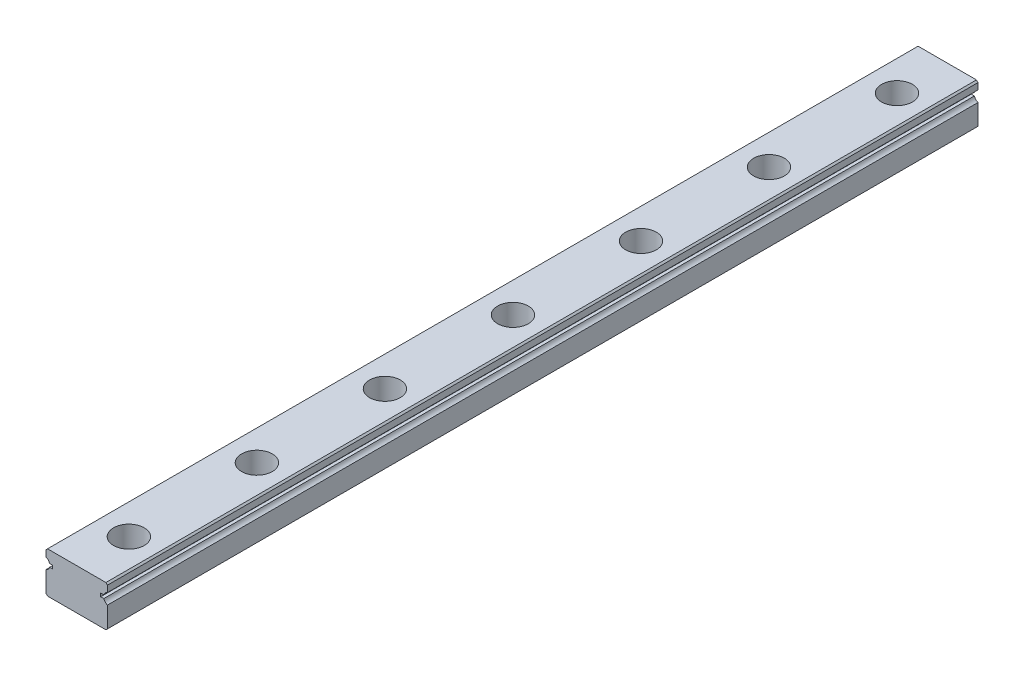
SolidWorks part; units mm, degrees
ref_plane "Спереди" through (0, 0, 0) normal (0, 0, 1) x (1, 0, 0)
ref_plane "Сверху" through (0, 0, 0) normal (0, 1, 0) x (1, 0, 0)
ref_plane "Справа" through (0, 0, 0) normal (1, 0, 0) x (0, 0, -1)
sketch "Эскиз1" plane through (0, 0, 0) normal (0, 0, 1) x (1, 0, 0)
  line L0 (-6, 3.7) -> (-5.7, 4)
  line L1 (-5.7, -4) -> (5.7, -4)
  line L2 (-6, -3.7) -> (-6, 0.3334)
  line L3 (-5.7, 4) -> (5.7, 4)
  line L4 (6, -3.7) -> (6, 0.3334)
  line L5 (-6, -4) -> (6, 4) construction
  line L6 (-6, 4) -> (6, -4) construction
  line L7 (-6, -3.7) -> (-5.7, -4)
  line L8 (5.7, -4) -> (6, -3.7)
  line L9 (5.7, 4) -> (6, 3.7)
  line L10 (-6, 2.4498) -> (-6, 3.7)
  line L11 (-5.2979, 1.7203) -> (-4.6875, 1.7203)
  line L12 (0, 5.4188) -> (0, -5.747) construction
  line L13 (-5.2922, 1.0823) -> (-4.6875, 1.0823)
  line L14 (-4.6875, 1.7203) -> (-4.6875, 1.0823)
  line L15 (4.6875, 1.7203) -> (4.6875, 1.0823)
  line L16 (5.2922, 1.0823) -> (4.6875, 1.0823)
  line L17 (5.2979, 1.7203) -> (4.6875, 1.7203)
  line L18 (6, 2.4498) -> (6, 3.7)
  arc A0 (-6, 0.3334) -> (-5.2922, 1.0823) centre (-6.3695, 1.3916) ccw
  arc A1 (-5.2979, 1.7203) -> (-6, 2.4498) centre (-6.3695, 1.3916) ccw
  arc A2 (5.2979, 1.7203) -> (6, 2.4498) centre (6.3695, 1.3916) cw
  arc A3 (6, 0.3334) -> (5.2922, 1.0823) centre (6.3695, 1.3916) cw
  point P0 (0, 0)
extrude "Бобышка-Вытянуть1" add sketch "Эскиз1" along normal blind 170
sketch "Эскиз2" plane through (0, 4, 0) normal (0, 1, 0) x (1, 0, 0)
  line L0 (0, 0) -> (0, -26.2396) construction
  line L1 (5.7, 0) -> (-5.7, 0) construction
  line L2 (-3.8306, -10) -> (4.207, -10) construction
  circle A0 centre (0.1882, -10) radius 3
  circle A1 centre (0.1882, -10) radius 1.75
  dimension "D1" = 10
extrude "Вырез-Вытянуть1" cut sketch "Эскиз2" against normal blind 4.5
extrude "Вырез-Вытянуть2" cut sketch "Эскиз2<2>" against normal through all contours A1 region at (0.1882, 4, 10)
sketch "Эскиз2<2>" plane through (0, 4, 0) normal (0, 1, 0) x (1, 0, 0) same geometry as "Эскиз2"
pattern_linear "Линейный массив1" count 12 spacing 25 along (0, 0, 1) of "Вырез-Вытянуть1", "Вырез-Вытянуть2"
